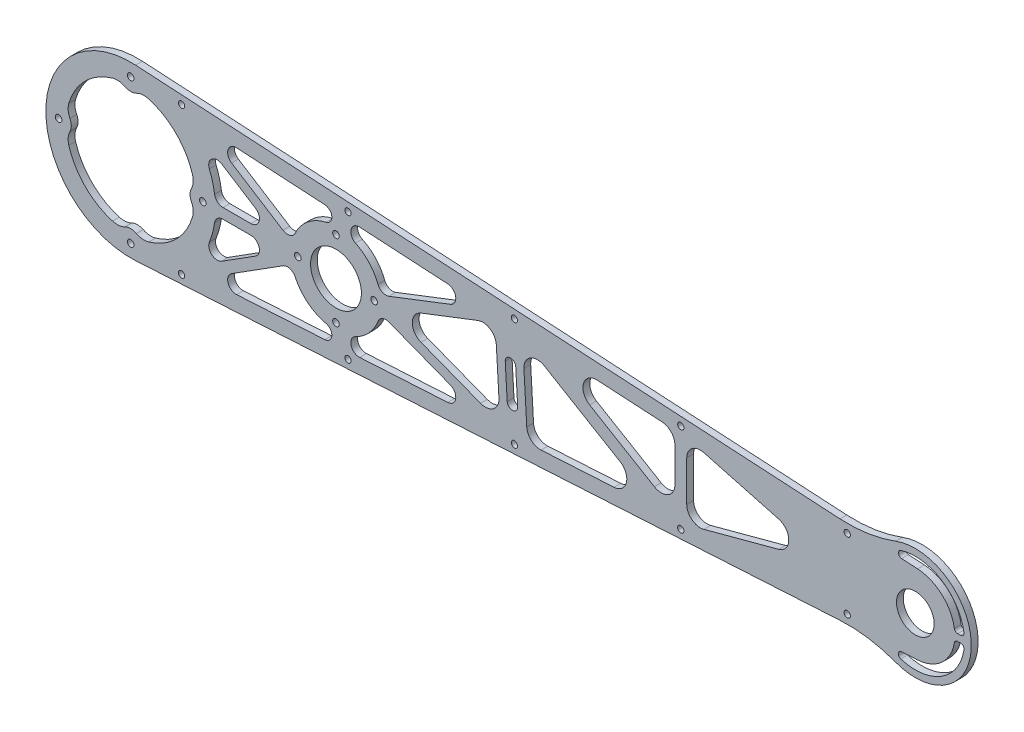
SolidWorks part; units mm, degrees
ref_plane "Front Plane" through (0, 0, 0) normal (0, 0, 1) x (1, 0, 0)
ref_plane "Top Plane" through (0, 0, 0) normal (0, 1, 0) x (1, 0, 0)
ref_plane "Right Plane" through (0, 0, 0) normal (1, 0, 0) x (0, 0, -1)
sketch "Sketch1" plane through (0, 0, 0) normal (0, 0, 1) x (1, 0, 0)
  line L0 (-231.25, 0) -> (231.25, 0) construction
  line L1 (-228.3622, 49.9165) -> (232.595, 23.2486)
  line L2 (-228.3622, -49.9165) -> (232.595, -23.2486)
  line L3 (191.094, 20.6412) -> (-201.25, 43.3396) construction
  line L4 (-103.164, -37.665) -> (-5.078, -31.9904) construction
  circle A0 centre (231.25, 0) radius 11.1125
  arc A1 (232.595, 23.2486) -> (232.595, -23.2486) centre (231.25, 0) cw
  circle A2 centre (-231.25, 0) radius 42.5 construction
  circle A3 centre (-110.25, 0) radius 22.5 construction
  arc A4 (-228.3622, 49.9165) -> (-228.3622, -49.9165) centre (-231.25, 0) ccw
  circle A5 centre (-231.25, 42.5) radius 1.75 construction
  circle A6 centre (-231.25, 0) radius 30
  circle A7 centre (-110.25, 0) radius 15
  circle A8 centre (231.25, 0) radius 35.306 construction
  circle A9 centre (-201.25, 43.3396) radius 1.85
  circle A10 centre (-103.164, 37.665) radius 1.85
  circle A11 centre (-5.078, 31.9904) radius 1.85
  circle A12 centre (93.008, 26.3158) radius 1.85
  circle A13 centre (191.094, 20.6412) radius 1.85
  circle A14 centre (289.1799, 14.9666) radius 1.85 construction
  circle A15 centre (191.094, -20.6412) radius 1.85
  circle A16 centre (93.008, -26.3158) radius 1.85
  circle A17 centre (-5.078, -31.9904) radius 1.85
  circle A18 centre (-103.164, -37.665) radius 1.85
  circle A19 centre (-201.25, -43.3396) radius 1.85
  point P4 (0, 0)
  point P15 (-231.25, 44.25)
  point P16 (-273.75, 0)
  point P17 (-231.25, 50)
  point P18 (-110.25, 22.5)
  point P19 (-231.25, -42.5)
  point P20 (-188.75, 0)
  point P21 (-132.75, 0)
  point P22 (-110.25, -22.5)
  point P23 (-87.75, 0)
  point P29 (0, 0)
  point P30 (0, 0)
  point P41 (0, 0)
  point P42 (0, 0)
  point P43 (0, 0)
  point P54 (94.3932, 26.2357)
  point P55 (94.3932, 26.2357)
  point P56 (190.9192, 20.6514)
  dimension "D2" = 22.225
  dimension "D3" = 85
  dimension "D5" = 45
  dimension "D6" = 3.5
  dimension "D7" = 7.5
  dimension "D9" = 60
  dimension "D10" = 30
  dimension "D11" = 70.612
  dimension "D13" = 3.7
  dimension "D16" = 6
  dimension "D1" = 462.5
  dimension "D4" = 121
  dimension "D12" = 5
  dimension "D14" = 30
  dimension "D17" = 393
extrude "Boss-Extrude1" add sketch "Sketch1" along normal blind 4
sketch "Sketch4" plane through (0, 0, 4) normal (0, 0, 1) x (1, 0, 0)
  point P0 (-231.25, 42.5)
  point P7 (-188.75, 0)
  point P10 (-132.75, 0)
  point P13 (-110.25, 22.5)
  point P16 (-87.75, 0)
  point P19 (-110.25, -22.5)
  point P24 (-273.75, 0)
  point P28 (-231.25, -42.5)
hole_wizard "M3.5 Clearance Hole1" positions "Sketch4" profile "Sketch6" hole size "M3.5" standard "ANSI Metric" end condition up to next
sketch "Sketch6" plane through (-231.25, 42.5, 4) normal (1, 0, 0) x (0, -1, 0)
  line L0 (0, 0) -> (0, 4)
  line L1 (0, 4) -> (1.95, 4)
  line L2 (1.95, 4) -> (1.95, 0)
  line L5 (1.95, 0) -> (0, 0)
  line L11 (0, -6.35) -> (0, 107.95) construction
  dimension "Thru Hole Dia." = 3.9
  dimension "Thru Hole Depth" = 4
sketch "Sketch7" plane through (0, 0, 4) normal (0, 0, 1) x (1, 0, 0)
  line L0 (93.008, 26.3158) -> (93.008, -26.3158) construction
  line L1 (93.008, -26.3158) -> (191.094, 0) construction
  line L2 (191.094, 0) -> (93.008, 26.3158) construction
  line L3 (191.094, 0) -> (-87.75, 0) construction
  line L4 (191.094, -20.6412) -> (191.094, 20.6412) construction
  line L5 (106.581, 19.5682) -> (150.7172, 7.7267)
  line L6 (150.7172, -7.7267) -> (106.581, -19.5682)
  line L7 (96.508, -11.8414) -> (96.508, 11.8414)
  line L8 (-5.078, -31.9904) -> (-9.0827, 37.2305) construction
  line L9 (-5.078, 31.9904) -> (93.008, -26.3158) construction
  line L10 (-5.078, 31.9904) -> (93.008, 26.3158) construction
  line L11 (-5.078, -31.9904) -> (93.008, -26.3158) construction
  line L12 (-87.75, 0) -> (-103.164, 37.665) construction
  line L13 (-103.164, 37.665) -> (-5.078, 31.9904) construction
  line L14 (-5.078, 31.9904) -> (-87.75, 0) construction
  line L15 (89.508, -5.5197) -> (89.508, 14.9611)
  line L16 (81.97, 22.9477) -> (43.8014, 25.1559)
  line L17 (39.2515, 10.2925) -> (77.4201, -12.3965)
  line L18 (12.6104, 16.8224) -> (57.2669, -9.7233)
  line L19 (53.6411, -24.5867) -> (10.6642, -27.073)
  line L20 (2.2155, -19.5484) -> (0.5359, 9.4836)
  line L21 (232.595, 23.2486) -> (-228.3622, 49.9165) construction
  line L22 (-228.3622, -49.9165) -> (232.595, -23.2486) construction
  line L23 (-14.1831, -13.1198) -> (-15.7202, 13.4491)
  line L24 (-26.5939, 20.448) -> (-60.156, 7.4609)
  line L25 (-60.156, -7.4609) -> (-25.0568, -21.0428)
  line L27 (-79.0253, 6.5929) -> (-42.8256, 20.6005)
  line L28 (-44.3412, 30.2553) -> (-96.2601, 33.2589)
  line L32 (-132.75, 0) -> (-188.75, 0) construction
  line L33 (-188.75, 0) -> (-201.25, 43.3396) construction
  line L34 (-201.25, 43.3396) -> (-132.75, 0) construction
  line L35 (-132.75, 0) -> (-103.164, 37.665) construction
  line L36 (-103.164, 37.665) -> (-201.25, 43.3396) construction
  line L37 (-171.7722, 28.2392) -> (-141.4788, 9.0727)
  line L39 (-116.7705, 34.4455) -> (-168.8101, 37.4562)
  line L41 (-176.8349, 3) -> (-160.3569, 3)
  line L42 (-157.6835, 12.2253) -> (-177.574, 24.8099)
  line L44 (-116.7705, -34.4455) -> (-168.8101, -37.4562)
  line L45 (-171.7722, -28.2392) -> (-141.4788, -9.0727)
  line L46 (-157.6835, -12.2253) -> (-177.574, -24.8099)
  line L48 (-176.8349, -3) -> (-160.3569, -3)
  line L50 (-44.3412, -30.2553) -> (-96.2601, -33.2589)
  line L51 (-79.0253, -6.5929) -> (-42.8256, -20.6005)
  line L52 (-103.164, -37.665) -> (-110.25, -22.5) construction
  line L53 (-113.0786, -28.2577) -> (-106.259, -42.8525) construction
  line L54 (-101.0351, -30.41) -> (-95.5118, -42.2307) construction
  line L55 (-6.2272, -12.127) -> (-7.3823, 7.8396) construction
  line L56 (-9.322, -12.306) -> (-10.4771, 7.6606)
  line L57 (-3.1324, -11.9479) -> (-4.2875, 8.0187)
  arc A0 (150.7172, 7.7267) -> (150.7172, -7.7267) centre (148.6441, 0) cw
  arc A1 (106.581, -19.5682) -> (96.508, -11.8414) centre (104.508, -11.8414) cw
  arc A2 (106.581, 19.5682) -> (96.508, 11.8414) centre (104.508, 11.8414) ccw
  arc A3 (89.508, 14.9611) -> (81.97, 22.9477) centre (81.508, 14.9611) ccw
  arc A4 (43.8014, 25.1559) -> (39.2515, 10.2925) centre (43.3394, 17.1693) ccw
  arc A5 (89.508, -5.5197) -> (77.4201, -12.3965) centre (81.508, -5.5197) cw
  arc A6 (57.2669, -9.7233) -> (53.6411, -24.5867) centre (53.1791, -16.6) cw
  arc A7 (10.6642, -27.073) -> (2.2155, -19.5484) centre (10.2022, -19.0864) cw
  arc A8 (12.6104, 16.8224) -> (0.5359, 9.4836) centre (8.5226, 9.9456) ccw
  arc A9 (-14.1831, -13.1198) -> (-25.0568, -21.0428) centre (-22.1698, -13.5819) cw
  arc A10 (-15.7202, 13.4491) -> (-26.5939, 20.448) centre (-23.7069, 12.9871) ccw
  arc A11 (-60.156, 7.4609) -> (-60.156, -7.4609) centre (-57.269, 0) ccw
  arc A12 (-42.8256, 20.6005) -> (-44.3412, 30.2553) centre (-44.63, 25.2636) ccw
  arc A18 (-171.7722, 28.2392) -> (-168.8101, 37.4562) centre (-169.0989, 32.4645) cw
  arc A21 (-160.3569, 3) -> (-157.6835, 12.2253) centre (-160.3569, 8) ccw
  arc A22 (-181.7818, 7.2727) -> (-176.8349, 3) centre (-176.8349, 8) ccw
  arc A23 (-184.8839, 18.7133) -> (-177.574, 24.8099) centre (-180.2473, 20.5846) cw
  arc A26 (-171.7722, -28.2392) -> (-168.8101, -37.4562) centre (-169.0989, -32.4645) ccw
  arc A27 (-184.8839, -18.7133) -> (-177.574, -24.8099) centre (-180.2473, -20.5846) ccw
  arc A28 (-181.7818, -7.2727) -> (-176.8349, -3) centre (-176.8349, -8) cw
  arc A29 (-160.3569, -3) -> (-157.6835, -12.2253) centre (-160.3569, -8) cw
  circle A30 centre (-110.25, 0) radius 15 construction
  circle A31 centre (-110.25, 0) radius 15 construction
  circle A32 centre (-110.25, 0) radius 22.5 construction
  arc A34 (-85.4996, 9.4693) -> (-98.7049, 23.8529) centre (-110.25, 0) ccw
  arc A37 (-85.4996, 9.4693) -> (-79.0253, 6.5929) centre (-80.8297, 11.2559) ccw
  arc A38 (-42.8256, -20.6005) -> (-44.3412, -30.2553) centre (-44.63, -25.2636) cw
  arc A39 (-96.2601, -33.2589) -> (-98.7049, -23.8529) centre (-96.5463, -28.3126) cw
  arc A40 (-134.2728, 11.1872) -> (-116.0666, 25.8538) centre (-110.25, 0) cw
  arc A41 (-85.4996, -9.4693) -> (-98.7049, -23.8529) centre (-110.25, 0) cw
  arc A42 (-85.4996, -9.4693) -> (-79.0253, -6.5929) centre (-80.8297, -11.2559) cw
  arc A43 (-116.7705, 34.4455) -> (-116.0666, 25.8538) centre (-117.0219, 30.1002) cw
  arc A44 (-134.2728, 11.1872) -> (-141.4788, 9.0727) centre (-138.8054, 13.298) cw
  arc A45 (-116.7705, -34.4455) -> (-116.0666, -25.8538) centre (-117.0219, -30.1002) ccw
  arc A46 (-134.2728, -11.1872) -> (-116.0666, -25.8538) centre (-110.25, 0) ccw
  arc A47 (-134.2728, -11.1872) -> (-141.4788, -9.0727) centre (-138.8054, -13.298) ccw
  arc A48 (-96.2601, 33.2589) -> (-98.7049, 23.8529) centre (-96.5463, 28.3126) ccw
  circle A49 centre (-5.078, -31.9904) radius 1.85 construction
  circle A50 centre (-5.078, -31.9904) radius 1.85
  arc A51 (-184.8839, 18.7133) -> (-181.7818, 7.2727) centre (-231.25, 0) cw
  arc A52 (-228.3622, 49.9165) -> (-228.3622, -49.9165) centre (-231.25, 0) ccw construction
  arc A53 (-228.3622, 49.9165) -> (-228.3622, -49.9165) centre (-231.25, 0) ccw
  arc A55 (-184.8839, -18.7133) -> (-181.7818, -7.2727) centre (-231.25, 0) ccw
  arc A56 (-9.322, -12.306) -> (-3.1324, -11.9479) centre (-6.2272, -12.127) ccw
  arc A57 (-4.2875, 8.0187) -> (-10.4771, 7.6606) centre (-7.3823, 7.8396) ccw
  point P36 (179.5167, 0)
  point P59 (-79.437, 0)
  point P102 (-113.0786, -28.2577)
  point P126 (-6.8048, -2.1437)
  dimension "D8" = 8
  dimension "D11" = 5
  dimension "D12" = 5
  dimension "D18" = 5
  dimension "D19" = 5
  dimension "D20" = 3.1
  dimension "D10" = 4
  dimension "D21" = 5
  dimension "D1" = 3
  dimension "D2" = 7
  dimension "D3" = 8
  dimension "D4" = 8
  dimension "D5" = 8
  dimension "D6" = 16
  dimension "D7" = 6
  dimension "D9" = 8
  dimension "D13" = 8
  dimension "D14" = 5
  dimension "D15" = 6
  dimension "D16" = 24.8967
  dimension "D17" = 6
  dimension "D22" = 20
extrude "Cut-Extrude1" cut sketch "Sketch7" against normal blind 10 contours A55 A27 L46 A29 L48 A28 | A23 A51 A22 L41 A21 L42 | A44 A40 A43 L39 A18 L37 | A46 A47 L45 A26 L44 A45 | A42 A41 A39 L50 A38 L51 | L28 A48 A34 A37 L27 A12 | L24 A11 L25 A9 L23 A10 | L18 A8 L20 A7 L19 A6 | L5 A2 L7 A1 L6 A0 | A5 L15 A3 L16 A4 L17 | L57 A57 L56 A56 region at (121.2449, 0, 4) region at (66.798, 9.2025, 4) region at (25.4746, -8.5651, 4) region at (-35.249, -0.2844, 4) region at (-71.8834, 22.3672, 4) region at (-143.7532, 26.2538, 4) region at (-171.7996, 12.3824, 4) region at (-143.7532, -26.2538, 4) region at (-171.7996, -12.3824, 4) region at (-71.8834, -22.3672, 4) region at (-6.8048, -2.1437, 4)
sketch "Sketch8" plane through (0, 0, 4) normal (0, 0, 1) x (1, 0, 0)
  arc A0 (-267.0517, -3.3738) -> (-267.0517, 3.3738) centre (-273.75, 0) ccw
  arc A1 (-267.7172, 10.6837) -> (-241.9337, 36.4672) centre (-231.25, 0) cw
  arc A2 (-228.3622, 49.9165) -> (-228.3622, -49.9165) centre (-231.25, 0) ccw construction
  arc A3 (-228.3622, 49.9165) -> (-228.3622, -49.9165) centre (-231.25, 0) ccw
  circle A4 centre (-273.75, 0) radius 1.95 construction
  circle A5 centre (-273.75, 0) radius 1.95
  arc A6 (-234.6238, 35.8017) -> (-227.8762, 35.8017) centre (-231.25, 42.5) ccw
  arc A7 (-220.5663, 36.4672) -> (-194.7828, 10.6837) centre (-231.25, 0) cw
  arc A8 (-195.4483, 3.3738) -> (-195.4483, -3.3738) centre (-188.75, 0) ccw
  arc A9 (-194.7828, -10.6837) -> (-220.5663, -36.4672) centre (-231.25, 0) cw
  arc A10 (-227.8762, -35.8017) -> (-234.6238, -35.8017) centre (-231.25, -42.5) ccw
  arc A11 (-241.9337, -36.4672) -> (-267.7172, -10.6837) centre (-231.25, 0) cw
  arc A12 (-241.9337, 36.4672) -> (-234.6238, 35.8017) centre (-239.1222, 26.8706) cw
  arc A13 (-227.8762, 35.8017) -> (-220.5663, 36.4672) centre (-223.3778, 26.8706) cw
  arc A14 (-194.7828, 10.6837) -> (-195.4483, 3.3738) centre (-204.3794, 7.8722) cw
  arc A15 (-195.4483, -3.3738) -> (-194.7828, -10.6837) centre (-204.3794, -7.8722) cw
  arc A16 (-220.5663, -36.4672) -> (-227.8762, -35.8017) centre (-223.3778, -26.8706) cw
  arc A17 (-234.6238, -35.8017) -> (-241.9337, -36.4672) centre (-239.1222, -26.8706) cw
  arc A18 (-267.0517, -3.3738) -> (-267.7172, -10.6837) centre (-258.1206, -7.8722) ccw
  arc A19 (-267.0517, 3.3738) -> (-267.7172, 10.6837) centre (-258.1206, 7.8722) cw
  point P24 (-231.25, 0)
  dimension "D1" = 12
  dimension "D3" = 10
  dimension "D2" = 4
extrude "Cut-Extrude2" cut sketch "Sketch8" against normal blind 10 contours A11 A10 A9 A8 A7 A6 A1 A0 region at (-231.25, 0, 4)
sketch "Sketch9" plane through (0, 0, 4) normal (0, 0, 1) x (1, 0, 0)
  line L2 (232.595, 23.2486) -> (-228.3622, 49.9165) construction
  line L3 (-228.3622, -49.9165) -> (232.595, -23.2486) construction
  line L4 (254.5375, 0) -> (264.25, 0) construction
  line L5 (254.4515, 2) -> (260.181, 2)
  line L6 (254.4515, -2) -> (260.181, -2)
  line L7 (215.3411, 24.2468) -> (209.2526, 24.5991)
  line L8 (215.3411, -24.2468) -> (209.2526, -24.5991)
  arc A1 (209.2526, -24.5991) -> (209.2526, 24.5991) centre (231.25, 0) ccw
  arc A2 (232.595, -23.2486) -> (232.595, 23.2486) centre (231.25, 0) ccw construction
  arc A3 (254.4515, -2) -> (254.4515, 2) centre (231.25, 0) ccw
  arc A4 (215.3411, 24.2468) -> (260.181, 2) centre (231.25, 0) cw
  arc A5 (260.181, -2) -> (215.3411, -24.2468) centre (231.25, 0) cw
  dimension "D1" = 33
  dimension "D2" = 4
  dimension "D3" = 4
extrude "Boss-Extrude2" add sketch "Sketch9" against normal up to surface (4 mm away) up to face at (118.288, 0, 0)
fillet "Fillet1" radius 2 6 edges at (215.3411, -24.2468, 2) (254.4515, -2, 2) (260.181, -2, 2) (254.4515, 2, 2) (260.181, 2, 2) (215.3411, 24.2468, 2)
fillet "Fillet2" radius 80 2 edges at (209.2526, 24.5991, 2) (209.2526, -24.5991, 2)
